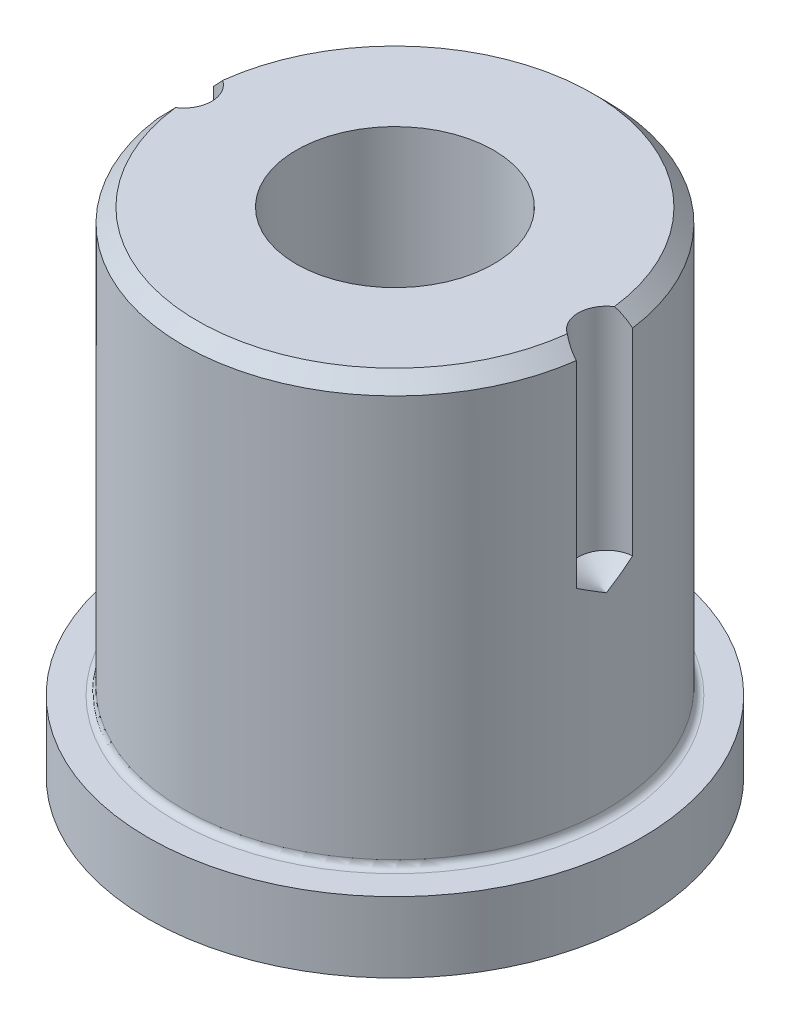
SolidWorks part; units mm, degrees
material "Commercial Bronze, UNS C22000 (90-10 Bronze)"
ref_plane "Front Plane" through (0, 0, 0) normal (0, 0, 1) x (1, 0, 0)
ref_plane "Top Plane" through (0, 0, 0) normal (0, 1, 0) x (1, 0, 0)
ref_plane "Right Plane" through (0, 0, 0) normal (1, 0, 0) x (0, 0, -1)
sketch "Sketch1" plane through (0, 0, 0) normal (0, 1, 0) x (1, 0, 0)
  circle A0 centre (0, 0) radius 35
  dimension "D1" = 70
extrude "Boss-Extrude1" add sketch "Sketch1" along normal blind 10
sketch "Sketch2" plane through (0, 10, 0) normal (0, 1, 0) x (1, 0, 0)
  circle A0 centre (0, 0) radius 30
  dimension "D1" = 60
extrude "Boss-Extrude2" add sketch "Sketch2" along normal blind 60
sketch "Sketch3" plane through (0, 70, 0) normal (0, 1, 0) x (1, 0, 0)
  circle A0 centre (0, 0) radius 14
  dimension "D1" = 28
extrude "Cut-Extrude1" cut sketch "Sketch3" against normal through all
chamfer "Chamfer1" distance 2 angle 45 1 edges at (0, 70, 30)
hole_wizard "Ø8.0mm Dowel Hole1" positions "Sketch4" profile "Sketch5" hole size "Ø8.0" standard "ISO"
sketch "Sketch4" plane through (0, 70, 0) normal (0, 1, 0) x (1, 0, 0)
  circle A0 centre (0, 0) radius 30 construction
  circle A1 centre (0, 0) radius 30 construction
  point P0 (-30, 0)
  point P4 (30, 0)
sketch "Sketch5" plane through (-30, 70, 0) normal (1, 0, 0) x (0, 0, 1)
  line L0 (0, 0) -> (0, 32.4034)
  line L1 (0, 32.4034) -> (4, 30)
  line L2 (4, 30) -> (4, 0)
  line L5 (4, 0) -> (0, 0)
  line L10 (0, 32.4034) -> (-4, 30) construction
  line L11 (0, -6.35) -> (0, 107.95) construction
  dimension "Hole Dia." = 8
  dimension "Hole Depth" = 30
  dimension "Drill Angle" = 118
fillet "Fillet1" radius 1 1 edges at (0, 10, 30)
